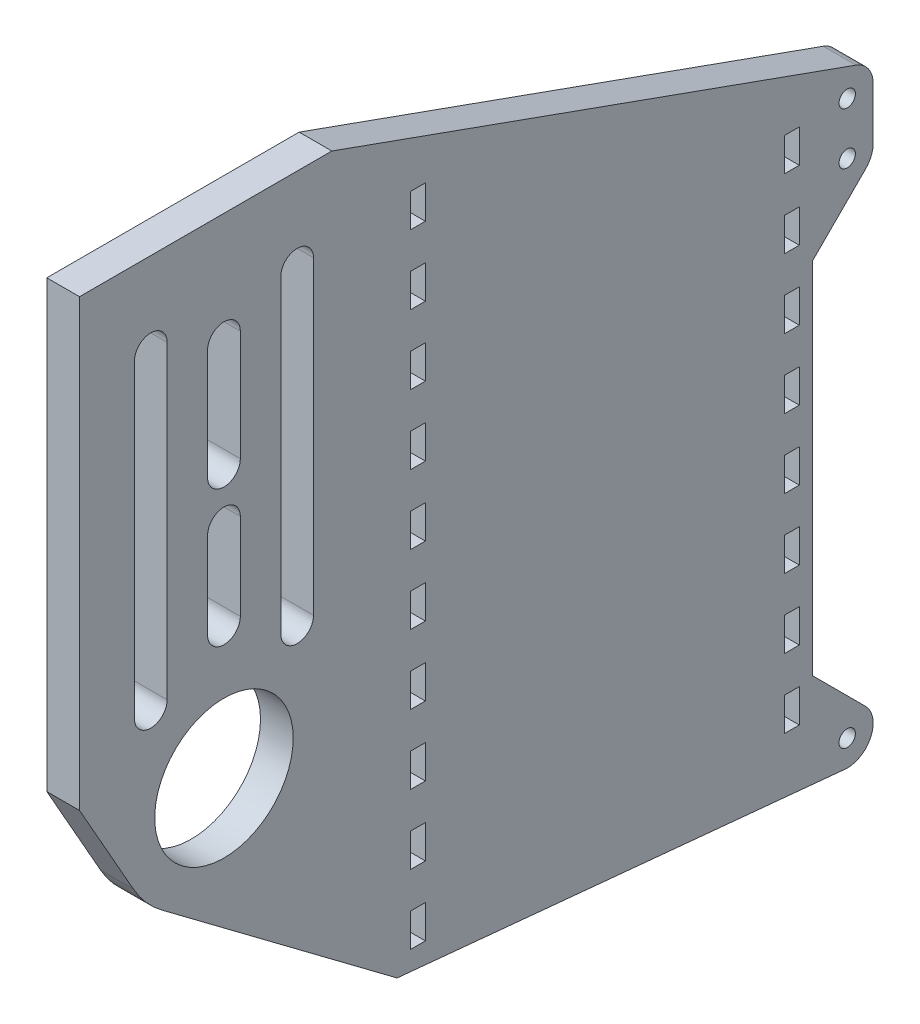
SolidWorks part; units mm, degrees
ref_plane "Front Plane" through (0, 0, 0) normal (0, 0, 1) x (1, 0, 0)
ref_plane "Top Plane" through (0, 0, 0) normal (0, 1, 0) x (1, 0, 0)
ref_plane "Right Plane" through (0, 0, 0) normal (1, 0, 0) x (0, 0, -1)
sketch "PlateGeometry" plane through (0, 0, 0) normal (1, 0, 0) x (0, 0, -1)
  line L1 (-38.1, -76.2) -> (38.1, -76.2) construction
  line L2 (-38.1, -76.2) -> (-38.1, 76.2) construction
  line L3 (-38.1, 76.2) -> (38.1, 76.2) construction
  line L4 (38.1, -76.2) -> (38.1, 76.2) construction
  line L5 (-38.1, -76.2) -> (38.1, 76.2) construction
  line L6 (-38.1, 76.2) -> (38.1, -76.2) construction
  line L11 (31.75, 76.2) -> (-31.75, 76.2) construction
  line L12 (31.75, 76.2) -> (31.75, -76.2) construction
  line L13 (31.75, -76.2) -> (-31.75, -76.2) construction
  line L14 (-31.75, 76.2) -> (-31.75, -76.2) construction
  line L15 (31.75, 76.2) -> (-31.75, -76.2) construction
  line L16 (31.75, -76.2) -> (-31.75, 76.2) construction
  point P0 (0, 0)
  point P6 (-44.4481, -57.148)
  point P7 (0, 0)
  point P8 (-43.0025, -57.15)
  point P9 (0, 0)
  point P14 (0, 0)
  point P15 (-43.2919, -50.698)
  line B0 (-35.7923, -66.6761) -> (-32.7923, -66.6739)
  line B1 (-35.7923, -66.6761) -> (-35.7877, -73.0261)
  line B2 (-35.7877, -73.0261) -> (-32.7877, -73.0239)
  line B3 (-32.7923, -66.6739) -> (-32.7877, -73.0239)
  line B4 (-35.7923, -66.6761) -> (-32.7877, -73.0239) construction
  line B5 (-35.7877, -73.0261) -> (-32.7923, -66.6739) construction
  line B6 (-35.7923, -53.9761) -> (-32.7923, -53.9739)
  line B7 (-35.7923, -53.9761) -> (-35.7877, -60.3261)
  line B8 (-35.7877, -60.3261) -> (-32.7877, -60.3239)
  line B9 (-32.7923, -53.9739) -> (-32.7877, -60.3239)
  line B10 (-35.7923, -53.9761) -> (-32.7877, -60.3239) construction
  line B11 (-35.7877, -60.3261) -> (-32.7923, -53.9739) construction
  line B12 (-35.7923, -41.2761) -> (-32.7923, -41.2739)
  line B13 (-35.7923, -41.2761) -> (-35.7877, -47.6261)
  line B14 (-35.7877, -47.6261) -> (-32.7877, -47.6239)
  line B15 (-32.7923, -41.2739) -> (-32.7877, -47.6239)
  line B16 (-35.7923, -41.2761) -> (-32.7877, -47.6239) construction
  line B17 (-35.7877, -47.6261) -> (-32.7923, -41.2739) construction
  line B18 (-35.7877, -34.9261) -> (-32.7877, -34.9239)
  line B19 (-32.7923, -28.5739) -> (-32.7877, -34.9239)
  line B20 (-35.7923, -15.8761) -> (-35.7877, -22.2261)
  line B21 (-35.7877, -22.2261) -> (-32.7877, -22.2239)
  line B22 (-32.7923, -15.8739) -> (-32.7877, -22.2239)
  line B23 (-35.7923, 9.5239) -> (-32.7923, 9.5261)
  line B24 (-32.7923, 9.5261) -> (-32.7877, 3.1761)
  line B25 (-35.7923, 9.5239) -> (-32.7877, 3.1761) construction
  line B26 (-35.7923, 22.2239) -> (-35.7877, 15.8739)
  line B27 (-35.7923, 34.9239) -> (-35.7877, 28.5739)
  line B28 (-35.7923, 47.6239) -> (-35.7877, 41.2739)
  line B29 (-35.7877, 41.2739) -> (-32.7923, 47.6261) construction
  line B30 (32.7886, -66.6757) -> (32.7914, -73.0257)
  line B31 (32.7914, -73.0257) -> (35.7914, -73.0243)
  line B32 (35.7886, -66.6743) -> (35.7914, -73.0243)
  line B33 (32.7886, -66.6757) -> (35.7914, -73.0243) construction
  line B34 (32.7914, -73.0257) -> (35.7886, -66.6743) construction
  line B35 (32.7886, -53.9757) -> (32.7914, -60.3257)
  line B36 (32.7914, -60.3257) -> (35.7914, -60.3243)
  line B37 (35.7886, -53.9743) -> (35.7914, -60.3243)
  line B38 (32.7886, -53.9757) -> (35.7914, -60.3243) construction
  line B39 (32.7914, -60.3257) -> (35.7886, -53.9743) construction
  line B40 (35.7886, -41.2743) -> (35.7914, -47.6243)
  line B41 (32.7914, -34.9257) -> (35.7914, -34.9243)
  line B42 (32.7886, -28.5757) -> (35.7914, -34.9243) construction
  line B43 (32.7886, -15.8757) -> (32.7914, -22.2257)
  line B44 (32.7886, -3.1757) -> (35.7914, -9.5243) construction
  line B45 (32.7914, -9.5257) -> (35.7886, -3.1743) construction
  line B46 (32.7886, 9.5243) -> (35.7886, 9.5257)
  line B47 (32.7886, 9.5243) -> (32.7914, 3.1743)
  line B48 (32.7914, 3.1743) -> (35.7914, 3.1757)
  line B49 (32.7886, 9.5243) -> (35.7914, 3.1757) construction
  line B50 (32.7886, 22.2243) -> (32.7914, 15.8743)
  line B51 (35.7886, 22.2257) -> (35.7914, 15.8757)
  line B52 (32.7886, 22.2243) -> (35.7914, 15.8757) construction
  line B53 (32.7914, 15.8743) -> (35.7886, 22.2257) construction
  line B54 (32.7914, 41.2743) -> (35.7914, 41.2757)
  line B55 (35.7886, 47.6257) -> (35.7914, 41.2757)
  line B56 (32.7886, 60.3243) -> (32.7914, 53.9743)
  line B57 (35.7886, 60.3257) -> (35.7914, 53.9757)
  line B58 (32.7886, 73.0243) -> (32.7914, 66.6743)
  line B59 (35.7886, 73.0257) -> (35.7914, 66.6757)
  line B60 (32.7914, 66.6743) -> (35.7886, 73.0257) construction
  circle B61 centre (-37.3063, -73.025) radius 5.5563 construction
  circle B62 centre (-37.3063, -73.025) radius 6.8263 construction
  circle B63 centre (-44.9262, -53.975) radius 5.5563 construction
  circle B64 centre (-44.9262, -53.975) radius 6.8263 construction
  dimension "D11" = 63.5
  dimension "D12" = 3.175
  dimension "D1" = 76.2
  dimension "D2" = 152.4
  dimension "D4" = 3.81
  dimension "D5" = 6.35
  dimension "D6" = 12.7
  dimension "D7" = 6.35
  dimension "D8" = 3.81
  dimension "D10" = 12.7
  dimension "D13" = 19.05
  dimension "D14" = 7.62
  dimension "D3" = 12
  dimension "D9" = 12
sketch_block_instance "SlotOutline-1"
sketch_block "SlotOutline" parameters "D1"=18.06, "D2"=7.2935
sketch_block_instance "SlotOutline-2"
sketch_block_instance "SlotOutline-3"
sketch_block_instance "SlotOutline-4"
sketch_block_instance "SlotOutline-5"
sketch_block_instance "SlotOutline-6"
sketch_block_instance "SlotOutline-7"
sketch_block_instance "SlotOutline-8"
sketch_block_instance "SlotOutline-9"
sketch_block_instance "SlotOutline-10"
sketch_block_instance "SlotOutline-11"
sketch_block_instance "SlotOutline-12"
sketch_block_instance "SlotOutline-13"
sketch_block_instance "SlotOutline-14"
sketch_block_instance "SlotOutline-15"
sketch_block_instance "SlotOutline-16"
sketch_block_instance "SlotOutline-17"
sketch_block_instance "SlotOutline-18"
sketch_block_instance "SlotOutline-19"
sketch_block_instance "SlotOutline-20"
sketch_block_instance "SlotOutline-21"
sketch_block_instance "SlotOutline-22"
sketch_block_instance "SlotOutline-23"
sketch_block_instance "SlotOutline-24"
sketch_block_instance "PulleyOutline-1"
sketch_block "PulleyOutline" parameters "D1"=11.1125, "D2"=13.6525
sketch_block_instance "PulleyOutline-2"
sketch "MotorGeometry" plane through (0, 0, 0) normal (1, 0, 0) x (0, 0, -1)
  line L0 (-83.2734, 1.775) -> (-83.2734, 49.025) construction
  line L3 (-50.2786, -55.4665) -> (-63.8121, -13.9087) construction
  line L4 (-41.2645, -76.9242) -> (-75.3216, -19.0975) construction
  line L5 (-38.1, -76.2) -> (-38.1, 76.2) construction
  line L6 (-38.1, -76.2) -> (38.1, -76.2) construction
  line L7 (38.1, -76.2) -> (38.1, 76.2) construction
  line L8 (-83.2734, 17.65) -> (-69.85, 9.9) construction
  line L9 (-69.85, 9.9) -> (-56.4266, 17.65) construction
  line L10 (-56.4266, 17.65) -> (-56.4266, 33.15) construction
  line L11 (-56.4266, 33.15) -> (-69.85, 40.9) construction
  line L12 (-69.85, 40.9) -> (-83.2734, 33.15) construction
  line L13 (-83.2734, 33.15) -> (-83.2734, 17.65) construction
  line L14 (-86.2734, 1.775) -> (-86.2734, 49.025)
  line L15 (-80.2734, 1.775) -> (-80.2734, 49.025)
  line L16 (-56.4266, 1.775) -> (-56.4266, 49.025) construction
  line L17 (-59.4266, 1.775) -> (-59.4266, 49.025)
  line L18 (-53.4266, 1.775) -> (-53.4266, 49.025)
  line L19 (-69.85, 8.3125) -> (-69.85, 47.25) construction
  line L20 (-72.85, 8.3125) -> (-72.85, 47.25)
  line L21 (-66.85, 8.3125) -> (-66.85, 47.25)
  circle A0 centre (44.45, -66.675) radius 1.5
  circle A1 centre (-69.85, -15.875) radius 11
  circle A5 centre (-69.85, -15.875) radius 30 construction
  circle A6 centre (-69.85, -15.875) radius 6.35 construction
  circle A7 centre (-44.9262, -53.975) radius 5.5562 construction
  circle A8 centre (-37.3063, -73.025) radius 5.5562 construction
  circle A9 centre (-69.85, -15.875) radius 25.5 construction
  circle A10 centre (-69.85, 25.4) radius 16 construction
  circle A11 centre (-69.85, 25.4) radius 11.5 construction
  circle A12 centre (-69.85, 25.4) radius 13.4234 construction
  arc A13 (-86.2734, 1.775) -> (-80.2734, 1.775) centre (-83.2734, 1.775) ccw
  arc A14 (-80.2734, 49.025) -> (-86.2734, 49.025) centre (-83.2734, 49.025) ccw
  arc A15 (-59.4266, 1.775) -> (-53.4266, 1.775) centre (-56.4266, 1.775) ccw
  arc A16 (-53.4266, 49.025) -> (-59.4266, 49.025) centre (-56.4266, 49.025) ccw
  arc A17 (-72.85, 8.3125) -> (-66.85, 8.3125) centre (-69.85, 8.3125) ccw
  arc A18 (-66.85, 47.25) -> (-72.85, 47.25) centre (-69.85, 47.25) ccw
  point P29 (-83.2734, 25.4)
  point P39 (-56.4266, 25.4)
  point P46 (-69.85, 27.7812)
  point P53 (0, 0)
  point P54 (-69.0453, 62.6709)
  point P55 (-72.3423, 70.6592)
  point P56 (-91.0269, 57.7021)
  point P57 (-67.8058, 4.4674)
  point P58 (0, 0)
  point P59 (-67.9361, 53.3841)
  point P60 (-54.0848, 47.9594)
  point P61 (-67.4577, 48.0424)
  point P62 (0, 0)
  point P63 (-71.6024, 27.9667)
  dimension "D1" = 22
  dimension "D4" = 60
  dimension "D5" = 12.7
  dimension "D7" = 4.5
  dimension "D8" = 32
  dimension "D9" = 4.5
  dimension "D13" = 3
  dimension "D3" = 6
  dimension "D2" = 31
  dimension "D6" = 38.1
  dimension "D10" = 31.75
  dimension "D11" = 9.525
  dimension "D12" = 6.35
  dimension "D14" = 15.875
  dimension "D15" = 1.5875
  dimension "D16" = 15.875
  dimension "D17" = 6.35
  dimension "D18" = 41.275
sketch "Sketch4" plane through (0, 0, 0) normal (1, 0, 0) x (0, 0, -1)
  line L0 (49.2125, 25.4) -> (49.2125, 34.925)
  line L1 (47.8176, 22.0324) -> (38.1, 12.3148)
  line L2 (-30.48, -50.8) -> (-38.1, -50.8) construction
  line L3 (-30.48, -50.8) -> (-30.48, -63.5) construction
  line L4 (-30.48, -63.5) -> (-38.1, -63.5) construction
  line L5 (-38.1, -50.8) -> (-38.1, -63.5) construction
  line L6 (-30.48, -50.8) -> (-38.1, -63.5) construction
  line L7 (-30.48, -63.5) -> (-38.1, -50.8) construction
  line L8 (38.1, 12.3148) -> (38.1, -53.5898)
  line L9 (38.1, -53.5898) -> (47.8176, -63.3074)
  line L10 (38.1, -76.2) -> (38.1, 76.2) construction
  line L11 (43.9929, -71.4155) -> (-38.1, -63.5)
  line L12 (-38.1, -63.5) -> (-81.28, -31.115)
  line L13 (-86.4236, -25.2674) -> (-96.3371, -7.7743)
  line L14 (-96.3371, -7.7743) -> (-96.3371, 73.8296)
  line L15 (-50.0636, 73.8296) -> (46.0556, 39.4087)
  line L16 (-96.3371, 73.8296) -> (-50.0636, 73.8296)
  line L17 (-83.2734, 1.775) -> (-83.2734, 58.55) construction
  line L18 (-86.2734, 1.775) -> (-86.2734, 58.55)
  line L19 (-80.2734, 1.775) -> (-80.2734, 58.55)
  line L20 (-69.85, 8.3125) -> (-69.85, 53.6) construction
  line L21 (-72.85, 8.3125) -> (-72.85, 53.6)
  line L22 (-66.85, 8.3125) -> (-66.85, 53.6)
  line L23 (-56.4266, 1.775) -> (-56.4266, 58.55) construction
  line L24 (-59.4266, 1.775) -> (-59.4266, 58.55)
  line L25 (-53.4266, 1.775) -> (-53.4266, 58.55)
  circle A0 centre (44.45, 25.4) radius 1.5
  circle A1 centre (44.45, 34.925) radius 1.5
  circle A2 centre (44.45, -66.675) radius 4.7625 construction
  circle A3 centre (44.45, 25.4) radius 4.7625 construction
  circle A4 centre (44.45, 34.925) radius 4.7625 construction
  circle A5 centre (-69.85, -15.875) radius 12.7
  arc A6 (43.9929, -71.4155) -> (47.8176, -63.3074) centre (44.45, -66.675) ccw
  circle A7 centre (-69.85, -15.875) radius 19.05
  arc A8 (47.8176, 22.0324) -> (49.2125, 25.4) centre (44.45, 25.4) ccw
  arc A9 (49.2125, 34.925) -> (46.0556, 39.4087) centre (44.45, 34.925) ccw
  circle A10 centre (44.45, -66.675) radius 1.5
  arc A11 (-86.2734, 1.775) -> (-80.2734, 1.775) centre (-83.2734, 1.775) ccw
  arc A12 (-80.2734, 58.55) -> (-86.2734, 58.55) centre (-83.2734, 58.55) ccw
  arc A13 (-72.85, 8.3125) -> (-66.85, 8.3125) centre (-69.85, 8.3125) ccw
  arc A14 (-66.85, 53.6) -> (-72.85, 53.6) centre (-69.85, 53.6) ccw
  arc A15 (-59.4266, 1.775) -> (-53.4266, 1.775) centre (-56.4266, 1.775) ccw
  arc A16 (-53.4266, 58.55) -> (-59.4266, 58.55) centre (-56.4266, 58.55) ccw
  arc A17 (-72.85, 24.1875) -> (-66.85, 24.1875) centre (-69.85, 24.1875) cw
  arc A18 (-72.85, 33.3625) -> (-66.85, 33.3625) centre (-69.85, 33.3625) ccw
  point P12 (-34.29, -57.15)
  point P36 (-83.2734, 30.1625)
  point P47 (-69.85, 30.9562)
  point P55 (-56.4266, 30.1625)
  point P71 (-50.0636, 73.8296)
  dimension "D1" = 3
  dimension "D4" = 9.525
  dimension "D9" = 25.4
  dimension "D10" = 38.1
  dimension "D11" = 6
  dimension "D14" = 3.175
  dimension "D2" = 9.525
  dimension "D3" = 101.6
  dimension "D5" = 3.81
  dimension "D6" = 12.7
  dimension "D7" = 45
  dimension "D8" = 45
  dimension "D12" = 12.7
  dimension "D13" = 25.4
  dimension "D15" = 15.875
extrude "Boss-Extrude1" add sketch "Sketch4" along normal mid plane 6 contours L0 A9 L13 A7 L12 L11 A6 L9 L8 L1 A8 A0 A1 | A7 A5 | A18 L21 A17 L22 region at (0, 2.6613, 19.3433) region at (0, 2.0245, 74.5693) region at (0, 28.775, 69.85)
sketch "Sketch5" plane through (3, 0, 0) normal (1, 0, 0) x (0, 0, -1)
  point P0 (36.2319, -54.4279)
  point P5 (35.7147, -57.7758)
  point P7 (31.453, -51.5077)
  point P13 (0, 0)
  line B0 (35.665, -54.102) -> (32.915, -54.102)
  line B1 (35.665, -54.102) -> (35.665, -60.198)
  line B2 (35.665, -60.198) -> (32.915, -60.198)
  line B3 (32.915, -54.102) -> (32.915, -60.198)
  line B4 (35.665, -54.102) -> (32.915, -60.198) construction
  line B5 (35.665, -60.198) -> (32.915, -54.102) construction
  line B6 (-32.915, -54.102) -> (-35.665, -54.102)
  line B7 (-32.915, -54.102) -> (-32.915, -60.198)
  line B8 (-32.915, -60.198) -> (-35.665, -60.198)
  line B9 (-35.665, -54.102) -> (-35.665, -60.198)
  line B10 (-32.915, -54.102) -> (-35.665, -60.198) construction
  line B11 (-32.915, -60.198) -> (-35.665, -54.102) construction
sketch_block_instance "Slot-1"
sketch_block "Slot" parameters "D1"=11.2845, "D2"=5.6739
sketch_block_instance "Slot-2"
extrude "LowerSlot" cut sketch "Sketch5" against normal through all both and the other way through all contours B0 B3 B2 B1 region at (3, -57.15, -34.29)
extrude "UpperSlot" cut sketch "Sketch5<3>" against normal through all both and the other way through all contours B6 B9 B8 B7 region at (3, -57.15, 34.29)
sketch "Sketch5<3>" plane through (3, 0, 0) normal (1, 0, 0) x (0, 0, -1) same geometry as "Sketch5"
pattern_linear "LowerSlots" count 8 spacing 12.7 along (0, 1, 0) of "LowerSlot"
pattern_linear "LPattern2" count 10 spacing 12.7 along (0, 1, 0) of "UpperSlot"
